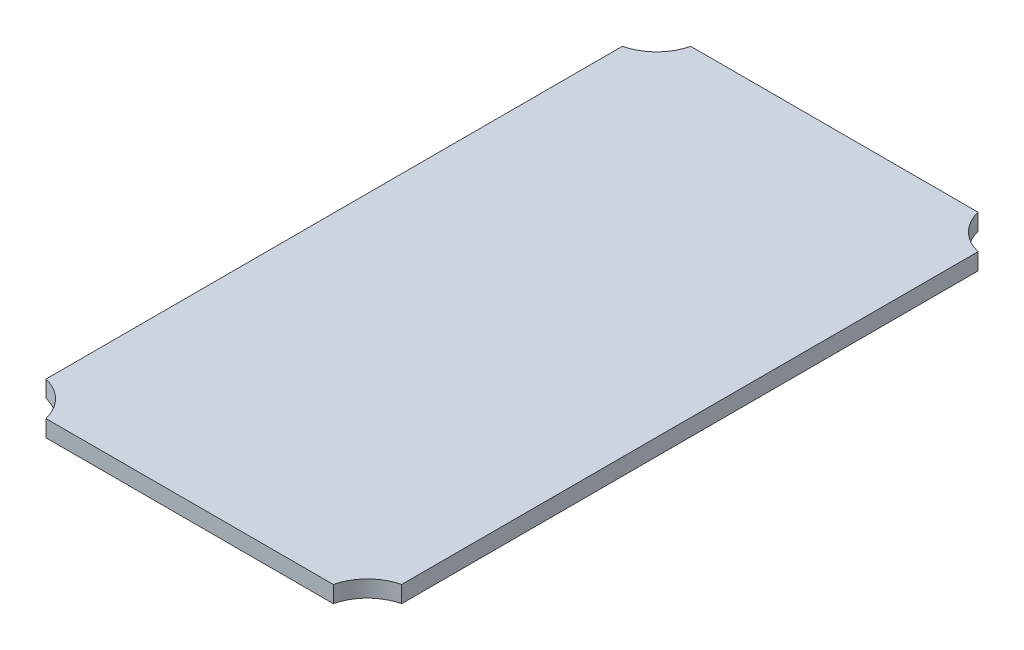
SolidWorks part; units mm, degrees
ref_plane "Front Plane" through (0, 0, 0) normal (0, 0, 1) x (1, 0, 0)
ref_plane "Top Plane" through (0, 0, 0) normal (0, 1, 0) x (1, 0, 0)
ref_plane "Right Plane" through (0, 0, 0) normal (1, 0, 0) x (0, 0, -1)
sketch "Sketch1" plane through (0, 0, 0) normal (0, 1, 0) x (1, 0, 0)
  line L1 (19, -32) -> (-19, -32)
  line L2 (19, -32) -> (19, 32)
  line L3 (19, 32) -> (-19, 32)
  line L4 (-19, -32) -> (-19, 32)
  line L5 (19, -32) -> (-19, 32) construction
  line L6 (19, 32) -> (-19, -32) construction
  line L7 (17, -30) -> (-17, -30)
  line L8 (17, -30) -> (17, 30)
  line L9 (17, 30) -> (-17, 30)
  line L10 (-17, -30) -> (-17, 30)
  line L11 (17, -30) -> (-17, 30) construction
  line L12 (17, 30) -> (-17, -30) construction
  point P0 (0, 0)
  point P6 (0, 0)
  dimension "D1" = 38
  dimension "D2" = 64
  dimension "D3" = 2
  dimension "D4" = 2
extrude "Boss-Extrude1" add sketch "Sketch1" along normal blind 1.5 contours L10 L7 L8 L9 region at (0, 0, 0)
sketch "Sketch5" plane through (0, 1.5, 0) normal (0, 1, 0) x (1, 0, 0)
  line L0 (-17, -30) -> (-17, 30) construction
  line L1 (17, 30) -> (-17, 30) construction
  line L2 (0, 30) -> (0, -30) construction
  line L3 (17, -30) -> (-17, -30) construction
  line L4 (-17, 25.8) -> (-17, 30)
  line L5 (17, -30) -> (17, 30) construction
  line L6 (17, 0) -> (-17, 0) construction
  line L7 (-17, 30) -> (-12.8, 30)
  line L8 (17, 30) -> (12.8, 30)
  line L9 (17, 25.8) -> (17, 30)
  line L10 (17, -25.8) -> (17, -30)
  line L11 (17, -30) -> (12.8, -30)
  line L12 (-17, -30) -> (-12.8, -30)
  line L13 (-17, -25.8) -> (-17, -30)
  arc A0 (-17, 25.8) -> (-12.8, 30) centre (-17, 30) ccw
  arc A1 (17, 25.8) -> (12.8, 30) centre (17, 30) cw
  arc A2 (17, -25.8) -> (12.8, -30) centre (17, -30) ccw
  arc A3 (-17, -25.8) -> (-12.8, -30) centre (-17, -30) cw
  dimension "D1" = 4.2
extrude "Cut-Extrude2" cut sketch "Sketch5" against normal blind 1.5
sketch "Sketch6" plane through (0, 1.5, 0) normal (0, 1, 0) x (1, 0, 0)
  line L0 (-17, -25.8) -> (-17, 25.8) construction
  line L1 (16, -29) -> (-16, -29)
  line L2 (16, -29) -> (16, 29)
  line L3 (16, 29) -> (-16, 29)
  line L4 (-16, -29) -> (-16, 29)
  line L5 (16, -29) -> (-16, 29) construction
  line L6 (16, 29) -> (-16, -29) construction
  line L7 (12.8, 30) -> (-12.8, 30) construction
  point P0 (0, 0)
  dimension "D1" = 1
  dimension "D2" = 1
extrude "Cut-Extrude3" cut sketch "Sketch6" against normal blind 1.5 flip side to cut
